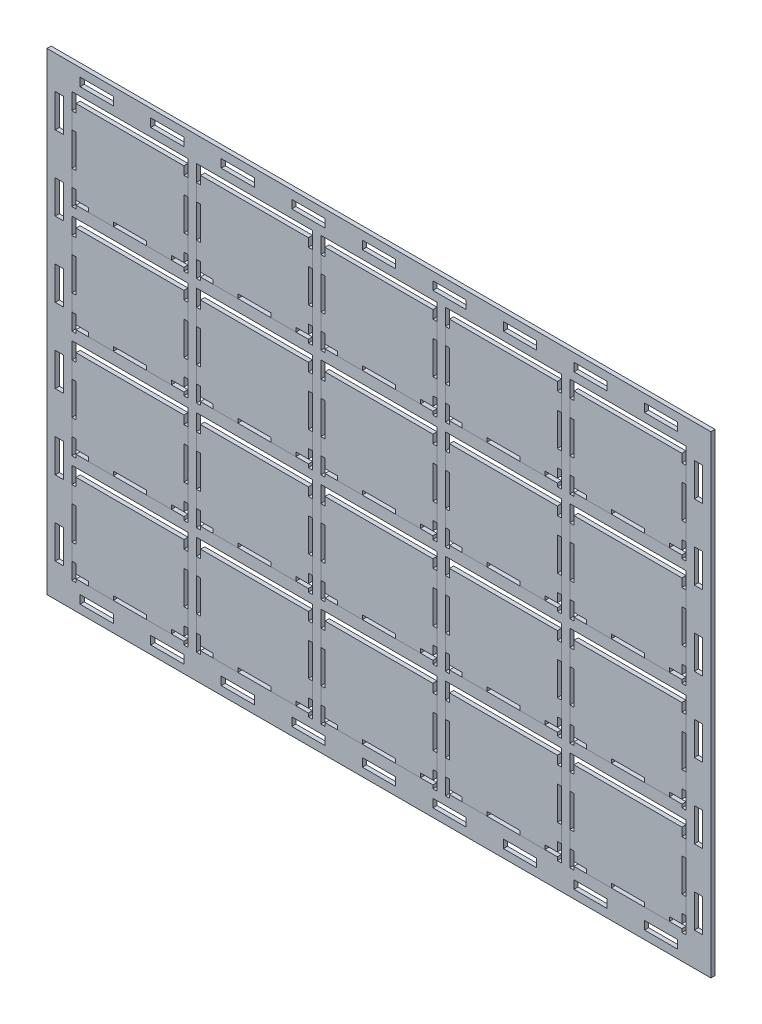
SolidWorks part; units mm, degrees
ref_plane "Front" through (0, 0, 0) normal (0, 0, 1) x (1, 0, 0)
ref_plane "Top" through (0, 0, 0) normal (0, 1, 0) x (1, 0, 0)
ref_plane "Right" through (0, 0, 0) normal (1, 0, 0) x (0, 0, -1)
sketch "Sketch1" plane through (0, 0, 0) normal (0, 0, 1) x (1, 0, 0)
  line L0 (-336.296, -110.6441) -> (-336.296, 164.3559) construction
  line L1 (-341.296, -115.6441) -> (58.704, -115.6441)
  line L2 (-341.296, -115.6441) -> (-341.296, 169.3559)
  line L3 (-341.296, 169.3559) -> (58.704, 169.3559)
  line L4 (58.704, -115.6441) -> (58.704, 169.3559)
  line L5 (-341.296, -115.6441) -> (58.704, 169.3559) construction
  line L6 (-341.296, 169.3559) -> (58.704, -115.6441) construction
  line L7 (-336.296, 164.3559) -> (53.704, 164.3559) construction
  line L8 (53.704, -110.6441) -> (53.704, 164.3559) construction
  line L9 (-336.296, -110.6441) -> (53.704, -110.6441) construction
  line L10 (-331.296, -105.6441) -> (-331.296, 159.3559) construction
  line L11 (-331.296, 159.3559) -> (48.704, 159.3559) construction
  line L12 (48.704, -105.6441) -> (48.704, 159.3559) construction
  line L13 (-331.296, -105.6441) -> (48.704, -105.6441) construction
  line L14 (-26.296, 96.3559) -> (43.704, 96.3559) construction
  line L15 (-26.296, 94.3559) -> (43.704, 94.3559) construction
  line L16 (-26.296, 94.3559) -> (-26.296, 154.3559) construction
  line L17 (-26.296, 154.3559) -> (43.704, 154.3559) construction
  line L18 (43.704, 94.3559) -> (43.704, 154.3559) construction
  line L19 (-26.296, 94.3559) -> (43.704, 154.3559) construction
  line L20 (-26.296, 154.3559) -> (43.704, 94.3559) construction
  line L21 (41.204, 154.3559) -> (41.204, 94.3559) construction
  line L22 (8.704, 134.2642) -> (8.704, 116.5512) construction
  line L23 (-23.796, 154.3559) -> (-23.796, 94.3559) construction
  line L24 (-26.296, 94.3559) -> (-26.296, 154.3559)
  line L25 (-26.296, 154.3559) -> (43.704, 154.3559)
  line L26 (43.704, 154.3559) -> (43.704, 94.3559)
  line L27 (43.704, 94.3559) -> (41.204, 94.3559)
  line L28 (41.204, 94.3559) -> (41.204, 96.3559)
  line L29 (-23.796, 94.3559) -> (-23.796, 96.3559)
  line L30 (-23.796, 96.3559) -> (41.204, 96.3559)
  line L31 (-23.796, 94.3559) -> (-26.296, 94.3559)
  line L32 (-23.796, 29.3559) -> (-26.296, 29.3559)
  line L33 (-26.296, 29.3559) -> (-26.296, 89.3559)
  line L34 (-26.296, 89.3559) -> (43.704, 89.3559)
  line L35 (43.704, 89.3559) -> (43.704, 29.3559)
  line L36 (43.704, 29.3559) -> (41.204, 29.3559)
  line L37 (41.204, 29.3559) -> (41.204, 31.3559)
  line L38 (-23.796, 31.3559) -> (41.204, 31.3559)
  line L39 (-23.796, 29.3559) -> (-23.796, 31.3559)
  line L40 (-23.796, -35.6441) -> (-26.296, -35.6441)
  line L41 (-26.296, -35.6441) -> (-26.296, 24.3559)
  line L42 (-26.296, 24.3559) -> (43.704, 24.3559)
  line L43 (43.704, 24.3559) -> (43.704, -35.6441)
  line L44 (43.704, -35.6441) -> (41.204, -35.6441)
  line L45 (41.204, -35.6441) -> (41.204, -33.6441)
  line L46 (-23.796, -33.6441) -> (41.204, -33.6441)
  line L47 (-23.796, -35.6441) -> (-23.796, -33.6441)
  line L48 (-23.796, -100.6441) -> (-26.296, -100.6441)
  line L49 (-26.296, -100.6441) -> (-26.296, -40.6441)
  line L50 (-26.296, -40.6441) -> (43.704, -40.6441)
  line L51 (43.704, -40.6441) -> (43.704, -100.6441)
  line L52 (43.704, -100.6441) -> (41.204, -100.6441)
  line L53 (41.204, -100.6441) -> (41.204, -98.6441)
  line L54 (-23.796, -98.6441) -> (41.204, -98.6441)
  line L55 (-23.796, -100.6441) -> (-23.796, -98.6441)
  line L56 (-98.796, 94.3559) -> (-101.296, 94.3559)
  line L57 (-101.296, 94.3559) -> (-101.296, 154.3559)
  line L58 (-101.296, 154.3559) -> (-31.296, 154.3559)
  line L59 (-31.296, 154.3559) -> (-31.296, 94.3559)
  line L60 (-31.296, 94.3559) -> (-33.796, 94.3559)
  line L61 (-33.796, 94.3559) -> (-33.796, 96.3559)
  line L62 (-98.796, 96.3559) -> (-33.796, 96.3559)
  line L63 (-98.796, 94.3559) -> (-98.796, 96.3559)
  line L64 (-98.796, 29.3559) -> (-101.296, 29.3559)
  line L65 (-101.296, 29.3559) -> (-101.296, 89.3559)
  line L66 (-101.296, 89.3559) -> (-31.296, 89.3559)
  line L67 (-31.296, 89.3559) -> (-31.296, 29.3559)
  line L68 (-31.296, 29.3559) -> (-33.796, 29.3559)
  line L69 (-33.796, 29.3559) -> (-33.796, 31.3559)
  line L70 (-98.796, 31.3559) -> (-33.796, 31.3559)
  line L71 (-98.796, 29.3559) -> (-98.796, 31.3559)
  line L72 (-98.796, -35.6441) -> (-101.296, -35.6441)
  line L73 (-101.296, -35.6441) -> (-101.296, 24.3559)
  line L74 (-101.296, 24.3559) -> (-31.296, 24.3559)
  line L75 (-31.296, 24.3559) -> (-31.296, -35.6441)
  line L76 (-31.296, -35.6441) -> (-33.796, -35.6441)
  line L77 (-33.796, -35.6441) -> (-33.796, -33.6441)
  line L78 (-98.796, -33.6441) -> (-33.796, -33.6441)
  line L79 (-98.796, -35.6441) -> (-98.796, -33.6441)
  line L80 (-98.796, -100.6441) -> (-101.296, -100.6441)
  line L81 (-101.296, -100.6441) -> (-101.296, -40.6441)
  line L82 (-101.296, -40.6441) -> (-31.296, -40.6441)
  line L83 (-31.296, -40.6441) -> (-31.296, -100.6441)
  line L84 (-31.296, -100.6441) -> (-33.796, -100.6441)
  line L85 (-33.796, -100.6441) -> (-33.796, -98.6441)
  line L86 (-98.796, -98.6441) -> (-33.796, -98.6441)
  line L87 (-98.796, -100.6441) -> (-98.796, -98.6441)
  line L88 (-173.796, 94.3559) -> (-176.296, 94.3559)
  line L89 (-176.296, 94.3559) -> (-176.296, 154.3559)
  line L90 (-176.296, 154.3559) -> (-106.296, 154.3559)
  line L91 (-106.296, 154.3559) -> (-106.296, 94.3559)
  line L92 (-106.296, 94.3559) -> (-108.796, 94.3559)
  line L93 (-108.796, 94.3559) -> (-108.796, 96.3559)
  line L94 (-173.796, 96.3559) -> (-108.796, 96.3559)
  line L95 (-173.796, 94.3559) -> (-173.796, 96.3559)
  line L96 (-173.796, 29.3559) -> (-176.296, 29.3559)
  line L97 (-176.296, 29.3559) -> (-176.296, 89.3559)
  line L98 (-176.296, 89.3559) -> (-106.296, 89.3559)
  line L99 (-106.296, 89.3559) -> (-106.296, 29.3559)
  line L100 (-106.296, 29.3559) -> (-108.796, 29.3559)
  line L101 (-108.796, 29.3559) -> (-108.796, 31.3559)
  line L102 (-173.796, 31.3559) -> (-108.796, 31.3559)
  line L103 (-173.796, 29.3559) -> (-173.796, 31.3559)
  line L104 (-173.796, -35.6441) -> (-176.296, -35.6441)
  line L105 (-176.296, -35.6441) -> (-176.296, 24.3559)
  line L106 (-176.296, 24.3559) -> (-106.296, 24.3559)
  line L107 (-106.296, 24.3559) -> (-106.296, -35.6441)
  line L108 (-106.296, -35.6441) -> (-108.796, -35.6441)
  line L109 (-108.796, -35.6441) -> (-108.796, -33.6441)
  line L110 (-173.796, -33.6441) -> (-108.796, -33.6441)
  line L111 (-173.796, -35.6441) -> (-173.796, -33.6441)
  line L112 (-173.796, -100.6441) -> (-176.296, -100.6441)
  line L113 (-176.296, -100.6441) -> (-176.296, -40.6441)
  line L114 (-176.296, -40.6441) -> (-106.296, -40.6441)
  line L115 (-106.296, -40.6441) -> (-106.296, -100.6441)
  line L116 (-106.296, -100.6441) -> (-108.796, -100.6441)
  line L117 (-108.796, -100.6441) -> (-108.796, -98.6441)
  line L118 (-173.796, -98.6441) -> (-108.796, -98.6441)
  line L119 (-173.796, -100.6441) -> (-173.796, -98.6441)
  line L120 (-248.796, 94.3559) -> (-251.296, 94.3559)
  line L121 (-251.296, 94.3559) -> (-251.296, 154.3559)
  line L122 (-251.296, 154.3559) -> (-181.296, 154.3559)
  line L123 (-181.296, 154.3559) -> (-181.296, 94.3559)
  line L124 (-181.296, 94.3559) -> (-183.796, 94.3559)
  line L125 (-183.796, 94.3559) -> (-183.796, 96.3559)
  line L126 (-248.796, 96.3559) -> (-183.796, 96.3559)
  line L127 (-248.796, 94.3559) -> (-248.796, 96.3559)
  line L128 (-248.796, 29.3559) -> (-251.296, 29.3559)
  line L129 (-251.296, 29.3559) -> (-251.296, 89.3559)
  line L130 (-251.296, 89.3559) -> (-181.296, 89.3559)
  line L131 (-181.296, 89.3559) -> (-181.296, 29.3559)
  line L132 (-181.296, 29.3559) -> (-183.796, 29.3559)
  line L133 (-183.796, 29.3559) -> (-183.796, 31.3559)
  line L134 (-248.796, 31.3559) -> (-183.796, 31.3559)
  line L135 (-248.796, 29.3559) -> (-248.796, 31.3559)
  line L136 (-248.796, -35.6441) -> (-251.296, -35.6441)
  line L137 (-251.296, -35.6441) -> (-251.296, 24.3559)
  line L138 (-251.296, 24.3559) -> (-181.296, 24.3559)
  line L139 (-181.296, 24.3559) -> (-181.296, -35.6441)
  line L140 (-181.296, -35.6441) -> (-183.796, -35.6441)
  line L141 (-183.796, -35.6441) -> (-183.796, -33.6441)
  line L142 (-248.796, -33.6441) -> (-183.796, -33.6441)
  line L143 (-248.796, -35.6441) -> (-248.796, -33.6441)
  line L144 (-248.796, -100.6441) -> (-251.296, -100.6441)
  line L145 (-251.296, -100.6441) -> (-251.296, -40.6441)
  line L146 (-251.296, -40.6441) -> (-181.296, -40.6441)
  line L147 (-181.296, -40.6441) -> (-181.296, -100.6441)
  line L148 (-181.296, -100.6441) -> (-183.796, -100.6441)
  line L149 (-183.796, -100.6441) -> (-183.796, -98.6441)
  line L150 (-248.796, -98.6441) -> (-183.796, -98.6441)
  line L151 (-248.796, -100.6441) -> (-248.796, -98.6441)
  line L152 (-323.796, 94.3559) -> (-326.296, 94.3559)
  line L153 (-326.296, 94.3559) -> (-326.296, 154.3559)
  line L154 (-326.296, 154.3559) -> (-256.296, 154.3559)
  line L155 (-256.296, 154.3559) -> (-256.296, 94.3559)
  line L156 (-256.296, 94.3559) -> (-258.796, 94.3559)
  line L157 (-258.796, 94.3559) -> (-258.796, 96.3559)
  line L158 (-323.796, 96.3559) -> (-258.796, 96.3559)
  line L159 (-323.796, 94.3559) -> (-323.796, 96.3559)
  line L160 (-323.796, 29.3559) -> (-326.296, 29.3559)
  line L161 (-326.296, 29.3559) -> (-326.296, 89.3559)
  line L162 (-326.296, 89.3559) -> (-256.296, 89.3559)
  line L163 (-256.296, 89.3559) -> (-256.296, 29.3559)
  line L164 (-256.296, 29.3559) -> (-258.796, 29.3559)
  line L165 (-258.796, 29.3559) -> (-258.796, 31.3559)
  line L166 (-323.796, 31.3559) -> (-258.796, 31.3559)
  line L167 (-323.796, 29.3559) -> (-323.796, 31.3559)
  line L168 (-323.796, -35.6441) -> (-326.296, -35.6441)
  line L169 (-326.296, -35.6441) -> (-326.296, 24.3559)
  line L170 (-326.296, 24.3559) -> (-256.296, 24.3559)
  line L171 (-256.296, 24.3559) -> (-256.296, -35.6441)
  line L172 (-256.296, -35.6441) -> (-258.796, -35.6441)
  line L173 (-258.796, -35.6441) -> (-258.796, -33.6441)
  line L174 (-323.796, -33.6441) -> (-258.796, -33.6441)
  line L175 (-323.796, -35.6441) -> (-323.796, -33.6441)
  line L176 (-323.796, -100.6441) -> (-326.296, -100.6441)
  line L177 (-326.296, -100.6441) -> (-326.296, -40.6441)
  line L178 (-326.296, -40.6441) -> (-256.296, -40.6441)
  line L179 (-256.296, -40.6441) -> (-256.296, -100.6441)
  line L180 (-256.296, -100.6441) -> (-258.796, -100.6441)
  line L181 (-258.796, -100.6441) -> (-258.796, -98.6441)
  line L182 (-323.796, -98.6441) -> (-258.796, -98.6441)
  line L183 (-323.796, -100.6441) -> (-323.796, -98.6441)
  line L184 (-119.2091, 26.8559) -> (-161.6715, 26.8559) construction
  line L185 (-321.296, 164.3559) -> (-301.296, 164.3559)
  line L186 (-321.296, 164.3559) -> (-321.296, 159.3559)
  line L187 (-321.296, 159.3559) -> (-301.296, 159.3559)
  line L188 (-301.296, 164.3559) -> (-301.296, 159.3559)
  line L189 (-321.296, 164.3559) -> (-301.296, 159.3559) construction
  line L190 (-321.296, 159.3559) -> (-301.296, 164.3559) construction
  line L191 (-141.296, 49.4928) -> (-141.296, 19.2296) construction
  line L192 (-321.296, -105.6441) -> (-301.296, -105.6441)
  line L193 (-301.296, -110.6441) -> (-301.296, -105.6441)
  line L194 (-321.296, -110.6441) -> (-301.296, -110.6441)
  line L195 (-321.296, -110.6441) -> (-321.296, -105.6441)
  line L196 (-278.796, 164.3559) -> (-278.796, 159.3559)
  line L197 (-278.796, 164.3559) -> (-258.796, 164.3559)
  line L198 (-258.796, 164.3559) -> (-258.796, 159.3559)
  line L199 (-278.796, 159.3559) -> (-258.796, 159.3559)
  line L200 (-278.796, -105.6441) -> (-258.796, -105.6441)
  line L201 (-258.796, -110.6441) -> (-258.796, -105.6441)
  line L202 (-278.796, -110.6441) -> (-258.796, -110.6441)
  line L203 (-278.796, -110.6441) -> (-278.796, -105.6441)
  line L204 (-236.296, 164.3559) -> (-236.296, 159.3559)
  line L205 (-236.296, 164.3559) -> (-216.296, 164.3559)
  line L206 (-216.296, 164.3559) -> (-216.296, 159.3559)
  line L207 (-236.296, 159.3559) -> (-216.296, 159.3559)
  line L208 (-236.296, -105.6441) -> (-216.296, -105.6441)
  line L209 (-216.296, -110.6441) -> (-216.296, -105.6441)
  line L210 (-236.296, -110.6441) -> (-216.296, -110.6441)
  line L211 (-236.296, -110.6441) -> (-236.296, -105.6441)
  line L212 (-193.796, 164.3559) -> (-193.796, 159.3559)
  line L213 (-193.796, 164.3559) -> (-173.796, 164.3559)
  line L214 (-173.796, 164.3559) -> (-173.796, 159.3559)
  line L215 (-193.796, 159.3559) -> (-173.796, 159.3559)
  line L216 (-193.796, -105.6441) -> (-173.796, -105.6441)
  line L217 (-173.796, -110.6441) -> (-173.796, -105.6441)
  line L218 (-193.796, -110.6441) -> (-173.796, -110.6441)
  line L219 (-193.796, -110.6441) -> (-193.796, -105.6441)
  line L220 (-151.296, 164.3559) -> (-151.296, 159.3559)
  line L221 (-151.296, 164.3559) -> (-131.296, 164.3559)
  line L222 (-131.296, 164.3559) -> (-131.296, 159.3559)
  line L223 (-151.296, 159.3559) -> (-131.296, 159.3559)
  line L224 (-151.296, -105.6441) -> (-131.296, -105.6441)
  line L225 (-131.296, -110.6441) -> (-131.296, -105.6441)
  line L226 (-151.296, -110.6441) -> (-131.296, -110.6441)
  line L227 (-151.296, -110.6441) -> (-151.296, -105.6441)
  line L228 (-108.796, 164.3559) -> (-108.796, 159.3559)
  line L229 (-108.796, 164.3559) -> (-88.796, 164.3559)
  line L230 (-88.796, 164.3559) -> (-88.796, 159.3559)
  line L231 (-108.796, 159.3559) -> (-88.796, 159.3559)
  line L232 (-108.796, -105.6441) -> (-88.796, -105.6441)
  line L233 (-88.796, -110.6441) -> (-88.796, -105.6441)
  line L234 (-108.796, -110.6441) -> (-88.796, -110.6441)
  line L235 (-108.796, -110.6441) -> (-108.796, -105.6441)
  line L236 (-66.296, 164.3559) -> (-66.296, 159.3559)
  line L237 (-66.296, 164.3559) -> (-46.296, 164.3559)
  line L238 (-46.296, 164.3559) -> (-46.296, 159.3559)
  line L239 (-66.296, 159.3559) -> (-46.296, 159.3559)
  line L240 (-66.296, -105.6441) -> (-46.296, -105.6441)
  line L241 (-46.296, -110.6441) -> (-46.296, -105.6441)
  line L242 (-66.296, -110.6441) -> (-46.296, -110.6441)
  line L243 (-66.296, -110.6441) -> (-66.296, -105.6441)
  line L244 (-23.796, 164.3559) -> (-23.796, 159.3559)
  line L245 (-23.796, 164.3559) -> (-3.796, 164.3559)
  line L246 (-3.796, 164.3559) -> (-3.796, 159.3559)
  line L247 (-23.796, 159.3559) -> (-3.796, 159.3559)
  line L248 (-23.796, -105.6441) -> (-3.796, -105.6441)
  line L249 (-3.796, -110.6441) -> (-3.796, -105.6441)
  line L250 (-23.796, -110.6441) -> (-3.796, -110.6441)
  line L251 (-23.796, -110.6441) -> (-23.796, -105.6441)
  line L252 (18.704, 164.3559) -> (18.704, 159.3559)
  line L253 (18.704, 164.3559) -> (38.704, 164.3559)
  line L254 (38.704, 164.3559) -> (38.704, 159.3559)
  line L255 (18.704, 159.3559) -> (38.704, 159.3559)
  line L256 (18.704, -105.6441) -> (38.704, -105.6441)
  line L257 (38.704, -110.6441) -> (38.704, -105.6441)
  line L258 (18.704, -110.6441) -> (38.704, -110.6441)
  line L259 (18.704, -110.6441) -> (18.704, -105.6441)
  line L260 (48.704, 129.3559) -> (53.704, 129.3559)
  line L261 (-331.296, 149.3559) -> (-336.296, 149.3559)
  line L262 (-331.296, 149.3559) -> (-331.296, 129.3559)
  line L263 (-331.296, 129.3559) -> (-336.296, 129.3559)
  line L264 (-336.296, 149.3559) -> (-336.296, 129.3559)
  line L265 (-331.296, 149.3559) -> (-336.296, 129.3559) construction
  line L266 (-331.296, 129.3559) -> (-336.296, 149.3559) construction
  line L267 (53.704, 149.3559) -> (53.704, 129.3559)
  line L268 (48.704, 149.3559) -> (53.704, 149.3559)
  line L269 (48.704, 149.3559) -> (48.704, 129.3559)
  line L270 (-331.296, 104.3559) -> (-331.296, 84.3559)
  line L271 (-331.296, 104.3559) -> (-336.296, 104.3559)
  line L272 (-336.296, 104.3559) -> (-336.296, 84.3559)
  line L273 (-331.296, 84.3559) -> (-336.296, 84.3559)
  line L274 (48.704, 84.3559) -> (53.704, 84.3559)
  line L275 (53.704, 104.3559) -> (53.704, 84.3559)
  line L276 (48.704, 104.3559) -> (53.704, 104.3559)
  line L277 (48.704, 104.3559) -> (48.704, 84.3559)
  line L278 (-331.296, 59.3559) -> (-331.296, 39.3559)
  line L279 (-331.296, 59.3559) -> (-336.296, 59.3559)
  line L280 (-336.296, 59.3559) -> (-336.296, 39.3559)
  line L281 (-331.296, 39.3559) -> (-336.296, 39.3559)
  line L282 (48.704, 39.3559) -> (53.704, 39.3559)
  line L283 (53.704, 59.3559) -> (53.704, 39.3559)
  line L284 (48.704, 59.3559) -> (53.704, 59.3559)
  line L285 (48.704, 59.3559) -> (48.704, 39.3559)
  line L286 (-331.296, 14.3559) -> (-331.296, -5.6441)
  line L287 (-331.296, 14.3559) -> (-336.296, 14.3559)
  line L288 (-336.296, 14.3559) -> (-336.296, -5.6441)
  line L289 (-331.296, -5.6441) -> (-336.296, -5.6441)
  line L290 (48.704, -5.6441) -> (53.704, -5.6441)
  line L291 (53.704, 14.3559) -> (53.704, -5.6441)
  line L292 (48.704, 14.3559) -> (53.704, 14.3559)
  line L293 (48.704, 14.3559) -> (48.704, -5.6441)
  line L294 (-331.296, -30.6441) -> (-331.296, -50.6441)
  line L295 (-331.296, -30.6441) -> (-336.296, -30.6441)
  line L296 (-336.296, -30.6441) -> (-336.296, -50.6441)
  line L297 (-331.296, -50.6441) -> (-336.296, -50.6441)
  line L298 (48.704, -50.6441) -> (53.704, -50.6441)
  line L299 (53.704, -30.6441) -> (53.704, -50.6441)
  line L300 (48.704, -30.6441) -> (53.704, -30.6441)
  line L301 (48.704, -30.6441) -> (48.704, -50.6441)
  line L302 (-331.296, -75.6441) -> (-331.296, -95.6441)
  line L303 (-331.296, -75.6441) -> (-336.296, -75.6441)
  line L304 (-336.296, -75.6441) -> (-336.296, -95.6441)
  line L305 (-331.296, -95.6441) -> (-336.296, -95.6441)
  line L306 (48.704, -95.6441) -> (53.704, -95.6441)
  line L307 (53.704, -75.6441) -> (53.704, -95.6441)
  line L308 (48.704, -75.6441) -> (53.704, -75.6441)
  line L309 (48.704, -75.6441) -> (48.704, -95.6441)
  line L310 (-26.296, 98.8559) -> (43.704, 98.8559) construction
  line L311 (-26.296, 94.3559) -> (43.704, 94.3559) construction
  line L312 (-26.296, 94.3559) -> (-26.296, 154.3559) construction
  line L313 (-26.296, 154.3559) -> (43.704, 154.3559) construction
  line L314 (43.704, 94.3559) -> (43.704, 154.3559) construction
  line L315 (-26.296, 94.3559) -> (43.704, 154.3559) construction
  line L316 (-26.296, 154.3559) -> (43.704, 94.3559) construction
  line L317 (8.704, 132.327) -> (8.704, 114.7588) construction
  line L318 (-16.296, 124.3559) -> (33.704, 124.3559) construction
  line L319 (-23.796, 154.3559) -> (-23.796, 94.3559) construction
  line L320 (41.204, 154.3559) -> (41.204, 94.3559) construction
  line L321 (33.704, 96.3559) -> (18.704, 96.3559)
  line L322 (-16.296, 98.8559) -> (-1.296, 98.8559) construction
  line L323 (-16.296, 98.8559) -> (-16.296, 96.3559)
  line L324 (-16.296, 96.3559) -> (-1.296, 96.3559)
  line L325 (-1.296, 98.8559) -> (-1.296, 96.3559)
  line L326 (-16.296, 98.8559) -> (-1.296, 96.3559) construction
  line L327 (-16.296, 96.3559) -> (-1.296, 98.8559) construction
  line L328 (18.704, 98.8559) -> (18.704, 96.3559)
  line L329 (33.704, 98.8559) -> (18.704, 98.8559) construction
  line L330 (33.704, 98.8559) -> (33.704, 96.3559)
  line L331 (-23.796, 114.3559) -> (-23.796, 134.3559)
  line L332 (-23.796, 134.3559) -> (-26.296, 134.3559)
  line L333 (-26.296, 134.3559) -> (-26.296, 144.3559)
  line L334 (-26.296, 144.3559) -> (-23.796, 144.3559)
  line L335 (-23.796, 144.3559) -> (-23.796, 154.3559) construction
  line L336 (-23.796, 154.3559) -> (41.204, 154.3559) construction
  line L337 (41.204, 144.3559) -> (41.204, 154.3559) construction
  line L338 (43.704, 144.3559) -> (41.204, 144.3559)
  line L339 (43.704, 134.3559) -> (43.704, 144.3559)
  line L340 (41.204, 134.3559) -> (43.704, 134.3559)
  line L341 (41.204, 114.3559) -> (41.204, 134.3559)
  line L342 (41.204, 114.3559) -> (43.704, 114.3559)
  line L343 (43.704, 114.3559) -> (43.704, 104.3559)
  line L344 (43.704, 104.3559) -> (41.204, 104.3559)
  line L345 (-23.796, 104.3559) -> (-23.796, 98.8559)
  line L346 (-23.796, 98.8559) -> (-16.296, 98.8559)
  line L347 (-26.296, 104.3559) -> (-23.796, 104.3559)
  line L348 (-26.296, 114.3559) -> (-26.296, 104.3559)
  line L349 (-23.796, 114.3559) -> (-26.296, 114.3559)
  line L350 (-23.796, 149.3559) -> (41.204, 149.3559)
  line L351 (-23.796, 149.3559) -> (-23.796, 144.3559)
  line L352 (41.204, 149.3559) -> (41.204, 144.3559)
  line L353 (-1.296, 98.8559) -> (18.704, 98.8559)
  line L354 (33.704, 98.8559) -> (41.204, 98.8559)
  line L355 (41.204, 98.8559) -> (41.204, 104.3559)
  line L356 (-1.296, 33.8559) -> (18.704, 33.8559)
  line L357 (18.704, 33.8559) -> (18.704, 31.3559)
  line L358 (33.704, 31.3559) -> (18.704, 31.3559)
  line L359 (33.704, 33.8559) -> (33.704, 31.3559)
  line L360 (33.704, 33.8559) -> (41.204, 33.8559)
  line L361 (41.204, 33.8559) -> (41.204, 39.3559)
  line L362 (43.704, 39.3559) -> (41.204, 39.3559)
  line L363 (43.704, 49.3559) -> (43.704, 39.3559)
  line L364 (41.204, 49.3559) -> (43.704, 49.3559)
  line L365 (41.204, 49.3559) -> (41.204, 69.3559)
  line L366 (41.204, 69.3559) -> (43.704, 69.3559)
  line L367 (43.704, 69.3559) -> (43.704, 79.3559)
  line L368 (43.704, 79.3559) -> (41.204, 79.3559)
  line L369 (41.204, 84.3559) -> (41.204, 79.3559)
  line L370 (-23.796, 84.3559) -> (41.204, 84.3559)
  line L371 (-23.796, 84.3559) -> (-23.796, 79.3559)
  line L372 (-26.296, 79.3559) -> (-23.796, 79.3559)
  line L373 (-26.296, 69.3559) -> (-26.296, 79.3559)
  line L374 (-23.796, 69.3559) -> (-26.296, 69.3559)
  line L375 (-23.796, 49.3559) -> (-23.796, 69.3559)
  line L376 (-23.796, 49.3559) -> (-26.296, 49.3559)
  line L377 (-26.296, 49.3559) -> (-26.296, 39.3559)
  line L378 (-26.296, 39.3559) -> (-23.796, 39.3559)
  line L379 (-23.796, 39.3559) -> (-23.796, 33.8559)
  line L380 (-23.796, 33.8559) -> (-16.296, 33.8559)
  line L381 (-16.296, 33.8559) -> (-16.296, 31.3559)
  line L382 (-16.296, 31.3559) -> (-1.296, 31.3559)
  line L383 (-1.296, 33.8559) -> (-1.296, 31.3559)
  line L384 (-1.296, -31.1441) -> (18.704, -31.1441)
  line L385 (18.704, -31.1441) -> (18.704, -33.6441)
  line L386 (33.704, -33.6441) -> (18.704, -33.6441)
  line L387 (33.704, -31.1441) -> (33.704, -33.6441)
  line L388 (33.704, -31.1441) -> (41.204, -31.1441)
  line L389 (41.204, -31.1441) -> (41.204, -25.6441)
  line L390 (43.704, -25.6441) -> (41.204, -25.6441)
  line L391 (43.704, -15.6441) -> (43.704, -25.6441)
  line L392 (41.204, -15.6441) -> (43.704, -15.6441)
  line L393 (41.204, -15.6441) -> (41.204, 4.3559)
  line L394 (41.204, 4.3559) -> (43.704, 4.3559)
  line L395 (43.704, 4.3559) -> (43.704, 14.3559)
  line L396 (43.704, 14.3559) -> (41.204, 14.3559)
  line L397 (41.204, 19.3559) -> (41.204, 14.3559)
  line L398 (-23.796, 19.3559) -> (41.204, 19.3559)
  line L399 (-23.796, 19.3559) -> (-23.796, 14.3559)
  line L400 (-26.296, 14.3559) -> (-23.796, 14.3559)
  line L401 (-26.296, 4.3559) -> (-26.296, 14.3559)
  line L402 (-23.796, 4.3559) -> (-26.296, 4.3559)
  line L403 (-23.796, -15.6441) -> (-23.796, 4.3559)
  line L404 (-23.796, -15.6441) -> (-26.296, -15.6441)
  line L405 (-26.296, -15.6441) -> (-26.296, -25.6441)
  line L406 (-26.296, -25.6441) -> (-23.796, -25.6441)
  line L407 (-23.796, -25.6441) -> (-23.796, -31.1441)
  line L408 (-23.796, -31.1441) -> (-16.296, -31.1441)
  line L409 (-16.296, -31.1441) -> (-16.296, -33.6441)
  line L410 (-16.296, -33.6441) -> (-1.296, -33.6441)
  line L411 (-1.296, -31.1441) -> (-1.296, -33.6441)
  line L412 (-1.296, -96.1441) -> (18.704, -96.1441)
  line L413 (18.704, -96.1441) -> (18.704, -98.6441)
  line L414 (33.704, -98.6441) -> (18.704, -98.6441)
  line L415 (33.704, -96.1441) -> (33.704, -98.6441)
  line L416 (33.704, -96.1441) -> (41.204, -96.1441)
  line L417 (41.204, -96.1441) -> (41.204, -90.6441)
  line L418 (43.704, -90.6441) -> (41.204, -90.6441)
  line L419 (43.704, -80.6441) -> (43.704, -90.6441)
  line L420 (41.204, -80.6441) -> (43.704, -80.6441)
  line L421 (41.204, -80.6441) -> (41.204, -60.6441)
  line L422 (41.204, -60.6441) -> (43.704, -60.6441)
  line L423 (43.704, -60.6441) -> (43.704, -50.6441)
  line L424 (43.704, -50.6441) -> (41.204, -50.6441)
  line L425 (41.204, -45.6441) -> (41.204, -50.6441)
  line L426 (-23.796, -45.6441) -> (41.204, -45.6441)
  line L427 (-23.796, -45.6441) -> (-23.796, -50.6441)
  line L428 (-26.296, -50.6441) -> (-23.796, -50.6441)
  line L429 (-26.296, -60.6441) -> (-26.296, -50.6441)
  line L430 (-23.796, -60.6441) -> (-26.296, -60.6441)
  line L431 (-23.796, -80.6441) -> (-23.796, -60.6441)
  line L432 (-23.796, -80.6441) -> (-26.296, -80.6441)
  line L433 (-26.296, -80.6441) -> (-26.296, -90.6441)
  line L434 (-26.296, -90.6441) -> (-23.796, -90.6441)
  line L435 (-23.796, -90.6441) -> (-23.796, -96.1441)
  line L436 (-23.796, -96.1441) -> (-16.296, -96.1441)
  line L437 (-16.296, -96.1441) -> (-16.296, -98.6441)
  line L438 (-16.296, -98.6441) -> (-1.296, -98.6441)
  line L439 (-1.296, -96.1441) -> (-1.296, -98.6441)
  line L440 (-76.296, 98.8559) -> (-56.296, 98.8559)
  line L441 (-56.296, 98.8559) -> (-56.296, 96.3559)
  line L442 (-41.296, 96.3559) -> (-56.296, 96.3559)
  line L443 (-41.296, 98.8559) -> (-41.296, 96.3559)
  line L444 (-41.296, 98.8559) -> (-33.796, 98.8559)
  line L445 (-33.796, 98.8559) -> (-33.796, 104.3559)
  line L446 (-31.296, 104.3559) -> (-33.796, 104.3559)
  line L447 (-31.296, 114.3559) -> (-31.296, 104.3559)
  line L448 (-33.796, 114.3559) -> (-31.296, 114.3559)
  line L449 (-33.796, 114.3559) -> (-33.796, 134.3559)
  line L450 (-33.796, 134.3559) -> (-31.296, 134.3559)
  line L451 (-31.296, 134.3559) -> (-31.296, 144.3559)
  line L452 (-31.296, 144.3559) -> (-33.796, 144.3559)
  line L453 (-33.796, 149.3559) -> (-33.796, 144.3559)
  line L454 (-98.796, 149.3559) -> (-33.796, 149.3559)
  line L455 (-98.796, 149.3559) -> (-98.796, 144.3559)
  line L456 (-101.296, 144.3559) -> (-98.796, 144.3559)
  line L457 (-101.296, 134.3559) -> (-101.296, 144.3559)
  line L458 (-98.796, 134.3559) -> (-101.296, 134.3559)
  line L459 (-98.796, 114.3559) -> (-98.796, 134.3559)
  line L460 (-98.796, 114.3559) -> (-101.296, 114.3559)
  line L461 (-101.296, 114.3559) -> (-101.296, 104.3559)
  line L462 (-101.296, 104.3559) -> (-98.796, 104.3559)
  line L463 (-98.796, 104.3559) -> (-98.796, 98.8559)
  line L464 (-98.796, 98.8559) -> (-91.296, 98.8559)
  line L465 (-91.296, 98.8559) -> (-91.296, 96.3559)
  line L466 (-91.296, 96.3559) -> (-76.296, 96.3559)
  line L467 (-76.296, 98.8559) -> (-76.296, 96.3559)
  line L468 (-76.296, 33.8559) -> (-56.296, 33.8559)
  line L469 (-56.296, 33.8559) -> (-56.296, 31.3559)
  line L470 (-41.296, 31.3559) -> (-56.296, 31.3559)
  line L471 (-41.296, 33.8559) -> (-41.296, 31.3559)
  line L472 (-41.296, 33.8559) -> (-33.796, 33.8559)
  line L473 (-33.796, 33.8559) -> (-33.796, 39.3559)
  line L474 (-31.296, 39.3559) -> (-33.796, 39.3559)
  line L475 (-31.296, 49.3559) -> (-31.296, 39.3559)
  line L476 (-33.796, 49.3559) -> (-31.296, 49.3559)
  line L477 (-33.796, 49.3559) -> (-33.796, 69.3559)
  line L478 (-33.796, 69.3559) -> (-31.296, 69.3559)
  line L479 (-31.296, 69.3559) -> (-31.296, 79.3559)
  line L480 (-31.296, 79.3559) -> (-33.796, 79.3559)
  line L481 (-33.796, 84.3559) -> (-33.796, 79.3559)
  line L482 (-98.796, 84.3559) -> (-33.796, 84.3559)
  line L483 (-98.796, 84.3559) -> (-98.796, 79.3559)
  line L484 (-101.296, 79.3559) -> (-98.796, 79.3559)
  line L485 (-101.296, 69.3559) -> (-101.296, 79.3559)
  line L486 (-98.796, 69.3559) -> (-101.296, 69.3559)
  line L487 (-98.796, 49.3559) -> (-98.796, 69.3559)
  line L488 (-98.796, 49.3559) -> (-101.296, 49.3559)
  line L489 (-101.296, 49.3559) -> (-101.296, 39.3559)
  line L490 (-101.296, 39.3559) -> (-98.796, 39.3559)
  line L491 (-98.796, 39.3559) -> (-98.796, 33.8559)
  line L492 (-98.796, 33.8559) -> (-91.296, 33.8559)
  line L493 (-91.296, 33.8559) -> (-91.296, 31.3559)
  line L494 (-91.296, 31.3559) -> (-76.296, 31.3559)
  line L495 (-76.296, 33.8559) -> (-76.296, 31.3559)
  line L496 (-76.296, -31.1441) -> (-56.296, -31.1441)
  line L497 (-56.296, -31.1441) -> (-56.296, -33.6441)
  line L498 (-41.296, -33.6441) -> (-56.296, -33.6441)
  line L499 (-41.296, -31.1441) -> (-41.296, -33.6441)
  line L500 (-41.296, -31.1441) -> (-33.796, -31.1441)
  line L501 (-33.796, -31.1441) -> (-33.796, -25.6441)
  line L502 (-31.296, -25.6441) -> (-33.796, -25.6441)
  line L503 (-31.296, -15.6441) -> (-31.296, -25.6441)
  line L504 (-33.796, -15.6441) -> (-31.296, -15.6441)
  line L505 (-33.796, -15.6441) -> (-33.796, 4.3559)
  line L506 (-33.796, 4.3559) -> (-31.296, 4.3559)
  line L507 (-31.296, 4.3559) -> (-31.296, 14.3559)
  line L508 (-31.296, 14.3559) -> (-33.796, 14.3559)
  line L509 (-33.796, 19.3559) -> (-33.796, 14.3559)
  line L510 (-98.796, 19.3559) -> (-33.796, 19.3559)
  line L511 (-98.796, 19.3559) -> (-98.796, 14.3559)
  line L512 (-101.296, 14.3559) -> (-98.796, 14.3559)
  line L513 (-101.296, 4.3559) -> (-101.296, 14.3559)
  line L514 (-98.796, 4.3559) -> (-101.296, 4.3559)
  line L515 (-98.796, -15.6441) -> (-98.796, 4.3559)
  line L516 (-98.796, -15.6441) -> (-101.296, -15.6441)
  line L517 (-101.296, -15.6441) -> (-101.296, -25.6441)
  line L518 (-101.296, -25.6441) -> (-98.796, -25.6441)
  line L519 (-98.796, -25.6441) -> (-98.796, -31.1441)
  line L520 (-98.796, -31.1441) -> (-91.296, -31.1441)
  line L521 (-91.296, -31.1441) -> (-91.296, -33.6441)
  line L522 (-91.296, -33.6441) -> (-76.296, -33.6441)
  line L523 (-76.296, -31.1441) -> (-76.296, -33.6441)
  line L524 (-76.296, -96.1441) -> (-56.296, -96.1441)
  line L525 (-56.296, -96.1441) -> (-56.296, -98.6441)
  line L526 (-41.296, -98.6441) -> (-56.296, -98.6441)
  line L527 (-41.296, -96.1441) -> (-41.296, -98.6441)
  line L528 (-41.296, -96.1441) -> (-33.796, -96.1441)
  line L529 (-33.796, -96.1441) -> (-33.796, -90.6441)
  line L530 (-31.296, -90.6441) -> (-33.796, -90.6441)
  line L531 (-31.296, -80.6441) -> (-31.296, -90.6441)
  line L532 (-33.796, -80.6441) -> (-31.296, -80.6441)
  line L533 (-33.796, -80.6441) -> (-33.796, -60.6441)
  line L534 (-33.796, -60.6441) -> (-31.296, -60.6441)
  line L535 (-31.296, -60.6441) -> (-31.296, -50.6441)
  line L536 (-31.296, -50.6441) -> (-33.796, -50.6441)
  line L537 (-33.796, -45.6441) -> (-33.796, -50.6441)
  line L538 (-98.796, -45.6441) -> (-33.796, -45.6441)
  line L539 (-98.796, -45.6441) -> (-98.796, -50.6441)
  line L540 (-101.296, -50.6441) -> (-98.796, -50.6441)
  line L541 (-101.296, -60.6441) -> (-101.296, -50.6441)
  line L542 (-98.796, -60.6441) -> (-101.296, -60.6441)
  line L543 (-98.796, -80.6441) -> (-98.796, -60.6441)
  line L544 (-98.796, -80.6441) -> (-101.296, -80.6441)
  line L545 (-101.296, -80.6441) -> (-101.296, -90.6441)
  line L546 (-101.296, -90.6441) -> (-98.796, -90.6441)
  line L547 (-98.796, -90.6441) -> (-98.796, -96.1441)
  line L548 (-98.796, -96.1441) -> (-91.296, -96.1441)
  line L549 (-91.296, -96.1441) -> (-91.296, -98.6441)
  line L550 (-91.296, -98.6441) -> (-76.296, -98.6441)
  line L551 (-76.296, -96.1441) -> (-76.296, -98.6441)
  line L552 (-151.296, 98.8559) -> (-131.296, 98.8559)
  line L553 (-131.296, 98.8559) -> (-131.296, 96.3559)
  line L554 (-116.296, 96.3559) -> (-131.296, 96.3559)
  line L555 (-116.296, 98.8559) -> (-116.296, 96.3559)
  line L556 (-116.296, 98.8559) -> (-108.796, 98.8559)
  line L557 (-108.796, 98.8559) -> (-108.796, 104.3559)
  line L558 (-106.296, 104.3559) -> (-108.796, 104.3559)
  line L559 (-106.296, 114.3559) -> (-106.296, 104.3559)
  line L560 (-108.796, 114.3559) -> (-106.296, 114.3559)
  line L561 (-108.796, 114.3559) -> (-108.796, 134.3559)
  line L562 (-108.796, 134.3559) -> (-106.296, 134.3559)
  line L563 (-106.296, 134.3559) -> (-106.296, 144.3559)
  line L564 (-106.296, 144.3559) -> (-108.796, 144.3559)
  line L565 (-108.796, 149.3559) -> (-108.796, 144.3559)
  line L566 (-173.796, 149.3559) -> (-108.796, 149.3559)
  line L567 (-173.796, 149.3559) -> (-173.796, 144.3559)
  line L568 (-176.296, 144.3559) -> (-173.796, 144.3559)
  line L569 (-176.296, 134.3559) -> (-176.296, 144.3559)
  line L570 (-173.796, 134.3559) -> (-176.296, 134.3559)
  line L571 (-173.796, 114.3559) -> (-173.796, 134.3559)
  line L572 (-173.796, 114.3559) -> (-176.296, 114.3559)
  line L573 (-176.296, 114.3559) -> (-176.296, 104.3559)
  line L574 (-176.296, 104.3559) -> (-173.796, 104.3559)
  line L575 (-173.796, 104.3559) -> (-173.796, 98.8559)
  line L576 (-173.796, 98.8559) -> (-166.296, 98.8559)
  line L577 (-166.296, 98.8559) -> (-166.296, 96.3559)
  line L578 (-166.296, 96.3559) -> (-151.296, 96.3559)
  line L579 (-151.296, 98.8559) -> (-151.296, 96.3559)
  line L580 (-151.296, 33.8559) -> (-131.296, 33.8559)
  line L581 (-131.296, 33.8559) -> (-131.296, 31.3559)
  line L582 (-116.296, 31.3559) -> (-131.296, 31.3559)
  line L583 (-116.296, 33.8559) -> (-116.296, 31.3559)
  line L584 (-116.296, 33.8559) -> (-108.796, 33.8559)
  line L585 (-108.796, 33.8559) -> (-108.796, 39.3559)
  line L586 (-106.296, 39.3559) -> (-108.796, 39.3559)
  line L587 (-106.296, 49.3559) -> (-106.296, 39.3559)
  line L588 (-108.796, 49.3559) -> (-106.296, 49.3559)
  line L589 (-108.796, 49.3559) -> (-108.796, 69.3559)
  line L590 (-108.796, 69.3559) -> (-106.296, 69.3559)
  line L591 (-106.296, 69.3559) -> (-106.296, 79.3559)
  line L592 (-106.296, 79.3559) -> (-108.796, 79.3559)
  line L593 (-108.796, 84.3559) -> (-108.796, 79.3559)
  line L594 (-173.796, 84.3559) -> (-108.796, 84.3559)
  line L595 (-173.796, 84.3559) -> (-173.796, 79.3559)
  line L596 (-176.296, 79.3559) -> (-173.796, 79.3559)
  line L597 (-176.296, 69.3559) -> (-176.296, 79.3559)
  line L598 (-173.796, 69.3559) -> (-176.296, 69.3559)
  line L599 (-173.796, 49.3559) -> (-173.796, 69.3559)
  line L600 (-173.796, 49.3559) -> (-176.296, 49.3559)
  line L601 (-176.296, 49.3559) -> (-176.296, 39.3559)
  line L602 (-176.296, 39.3559) -> (-173.796, 39.3559)
  line L603 (-173.796, 39.3559) -> (-173.796, 33.8559)
  line L604 (-173.796, 33.8559) -> (-166.296, 33.8559)
  line L605 (-166.296, 33.8559) -> (-166.296, 31.3559)
  line L606 (-166.296, 31.3559) -> (-151.296, 31.3559)
  line L607 (-151.296, 33.8559) -> (-151.296, 31.3559)
  line L608 (-151.296, -31.1441) -> (-131.296, -31.1441)
  line L609 (-131.296, -31.1441) -> (-131.296, -33.6441)
  line L610 (-116.296, -33.6441) -> (-131.296, -33.6441)
  line L611 (-116.296, -31.1441) -> (-116.296, -33.6441)
  line L612 (-116.296, -31.1441) -> (-108.796, -31.1441)
  line L613 (-108.796, -31.1441) -> (-108.796, -25.6441)
  line L614 (-106.296, -25.6441) -> (-108.796, -25.6441)
  line L615 (-106.296, -15.6441) -> (-106.296, -25.6441)
  line L616 (-108.796, -15.6441) -> (-106.296, -15.6441)
  line L617 (-108.796, -15.6441) -> (-108.796, 4.3559)
  line L618 (-108.796, 4.3559) -> (-106.296, 4.3559)
  line L619 (-106.296, 4.3559) -> (-106.296, 14.3559)
  line L620 (-106.296, 14.3559) -> (-108.796, 14.3559)
  line L621 (-108.796, 19.3559) -> (-108.796, 14.3559)
  line L622 (-173.796, 19.3559) -> (-108.796, 19.3559)
  line L623 (-173.796, 19.3559) -> (-173.796, 14.3559)
  line L624 (-176.296, 14.3559) -> (-173.796, 14.3559)
  line L625 (-176.296, 4.3559) -> (-176.296, 14.3559)
  line L626 (-173.796, 4.3559) -> (-176.296, 4.3559)
  line L627 (-173.796, -15.6441) -> (-173.796, 4.3559)
  line L628 (-173.796, -15.6441) -> (-176.296, -15.6441)
  line L629 (-176.296, -15.6441) -> (-176.296, -25.6441)
  line L630 (-176.296, -25.6441) -> (-173.796, -25.6441)
  line L631 (-173.796, -25.6441) -> (-173.796, -31.1441)
  line L632 (-173.796, -31.1441) -> (-166.296, -31.1441)
  line L633 (-166.296, -31.1441) -> (-166.296, -33.6441)
  line L634 (-166.296, -33.6441) -> (-151.296, -33.6441)
  line L635 (-151.296, -31.1441) -> (-151.296, -33.6441)
  line L636 (-151.296, -96.1441) -> (-131.296, -96.1441)
  line L637 (-131.296, -96.1441) -> (-131.296, -98.6441)
  line L638 (-116.296, -98.6441) -> (-131.296, -98.6441)
  line L639 (-116.296, -96.1441) -> (-116.296, -98.6441)
  line L640 (-116.296, -96.1441) -> (-108.796, -96.1441)
  line L641 (-108.796, -96.1441) -> (-108.796, -90.6441)
  line L642 (-106.296, -90.6441) -> (-108.796, -90.6441)
  line L643 (-106.296, -80.6441) -> (-106.296, -90.6441)
  line L644 (-108.796, -80.6441) -> (-106.296, -80.6441)
  line L645 (-108.796, -80.6441) -> (-108.796, -60.6441)
  line L646 (-108.796, -60.6441) -> (-106.296, -60.6441)
  line L647 (-106.296, -60.6441) -> (-106.296, -50.6441)
  line L648 (-106.296, -50.6441) -> (-108.796, -50.6441)
  line L649 (-108.796, -45.6441) -> (-108.796, -50.6441)
  line L650 (-173.796, -45.6441) -> (-108.796, -45.6441)
  line L651 (-173.796, -45.6441) -> (-173.796, -50.6441)
  line L652 (-176.296, -50.6441) -> (-173.796, -50.6441)
  line L653 (-176.296, -60.6441) -> (-176.296, -50.6441)
  line L654 (-173.796, -60.6441) -> (-176.296, -60.6441)
  line L655 (-173.796, -80.6441) -> (-173.796, -60.6441)
  line L656 (-173.796, -80.6441) -> (-176.296, -80.6441)
  line L657 (-176.296, -80.6441) -> (-176.296, -90.6441)
  line L658 (-176.296, -90.6441) -> (-173.796, -90.6441)
  line L659 (-173.796, -90.6441) -> (-173.796, -96.1441)
  line L660 (-173.796, -96.1441) -> (-166.296, -96.1441)
  line L661 (-166.296, -96.1441) -> (-166.296, -98.6441)
  line L662 (-166.296, -98.6441) -> (-151.296, -98.6441)
  line L663 (-151.296, -96.1441) -> (-151.296, -98.6441)
  line L664 (-226.296, 98.8559) -> (-206.296, 98.8559)
  line L665 (-206.296, 98.8559) -> (-206.296, 96.3559)
  line L666 (-191.296, 96.3559) -> (-206.296, 96.3559)
  line L667 (-191.296, 98.8559) -> (-191.296, 96.3559)
  line L668 (-191.296, 98.8559) -> (-183.796, 98.8559)
  line L669 (-183.796, 98.8559) -> (-183.796, 104.3559)
  line L670 (-181.296, 104.3559) -> (-183.796, 104.3559)
  line L671 (-181.296, 114.3559) -> (-181.296, 104.3559)
  line L672 (-183.796, 114.3559) -> (-181.296, 114.3559)
  line L673 (-183.796, 114.3559) -> (-183.796, 134.3559)
  line L674 (-183.796, 134.3559) -> (-181.296, 134.3559)
  line L675 (-181.296, 134.3559) -> (-181.296, 144.3559)
  line L676 (-181.296, 144.3559) -> (-183.796, 144.3559)
  line L677 (-183.796, 149.3559) -> (-183.796, 144.3559)
  line L678 (-248.796, 149.3559) -> (-183.796, 149.3559)
  line L679 (-248.796, 149.3559) -> (-248.796, 144.3559)
  line L680 (-251.296, 144.3559) -> (-248.796, 144.3559)
  line L681 (-251.296, 134.3559) -> (-251.296, 144.3559)
  line L682 (-248.796, 134.3559) -> (-251.296, 134.3559)
  line L683 (-248.796, 114.3559) -> (-248.796, 134.3559)
  line L684 (-248.796, 114.3559) -> (-251.296, 114.3559)
  line L685 (-251.296, 114.3559) -> (-251.296, 104.3559)
  line L686 (-251.296, 104.3559) -> (-248.796, 104.3559)
  line L687 (-248.796, 104.3559) -> (-248.796, 98.8559)
  line L688 (-248.796, 98.8559) -> (-241.296, 98.8559)
  line L689 (-241.296, 98.8559) -> (-241.296, 96.3559)
  line L690 (-241.296, 96.3559) -> (-226.296, 96.3559)
  line L691 (-226.296, 98.8559) -> (-226.296, 96.3559)
  line L692 (-226.296, 33.8559) -> (-206.296, 33.8559)
  line L693 (-206.296, 33.8559) -> (-206.296, 31.3559)
  line L694 (-191.296, 31.3559) -> (-206.296, 31.3559)
  line L695 (-191.296, 33.8559) -> (-191.296, 31.3559)
  line L696 (-191.296, 33.8559) -> (-183.796, 33.8559)
  line L697 (-183.796, 33.8559) -> (-183.796, 39.3559)
  line L698 (-181.296, 39.3559) -> (-183.796, 39.3559)
  line L699 (-181.296, 49.3559) -> (-181.296, 39.3559)
  line L700 (-183.796, 49.3559) -> (-181.296, 49.3559)
  line L701 (-183.796, 49.3559) -> (-183.796, 69.3559)
  line L702 (-183.796, 69.3559) -> (-181.296, 69.3559)
  line L703 (-181.296, 69.3559) -> (-181.296, 79.3559)
  line L704 (-181.296, 79.3559) -> (-183.796, 79.3559)
  line L705 (-183.796, 84.3559) -> (-183.796, 79.3559)
  line L706 (-248.796, 84.3559) -> (-183.796, 84.3559)
  line L707 (-248.796, 84.3559) -> (-248.796, 79.3559)
  line L708 (-251.296, 79.3559) -> (-248.796, 79.3559)
  line L709 (-251.296, 69.3559) -> (-251.296, 79.3559)
  line L710 (-248.796, 69.3559) -> (-251.296, 69.3559)
  line L711 (-248.796, 49.3559) -> (-248.796, 69.3559)
  line L712 (-248.796, 49.3559) -> (-251.296, 49.3559)
  line L713 (-251.296, 49.3559) -> (-251.296, 39.3559)
  line L714 (-251.296, 39.3559) -> (-248.796, 39.3559)
  line L715 (-248.796, 39.3559) -> (-248.796, 33.8559)
  line L716 (-248.796, 33.8559) -> (-241.296, 33.8559)
  line L717 (-241.296, 33.8559) -> (-241.296, 31.3559)
  line L718 (-241.296, 31.3559) -> (-226.296, 31.3559)
  line L719 (-226.296, 33.8559) -> (-226.296, 31.3559)
  line L720 (-226.296, -31.1441) -> (-206.296, -31.1441)
  line L721 (-206.296, -31.1441) -> (-206.296, -33.6441)
  line L722 (-191.296, -33.6441) -> (-206.296, -33.6441)
  line L723 (-191.296, -31.1441) -> (-191.296, -33.6441)
  line L724 (-191.296, -31.1441) -> (-183.796, -31.1441)
  line L725 (-183.796, -31.1441) -> (-183.796, -25.6441)
  line L726 (-181.296, -25.6441) -> (-183.796, -25.6441)
  line L727 (-181.296, -15.6441) -> (-181.296, -25.6441)
  line L728 (-183.796, -15.6441) -> (-181.296, -15.6441)
  line L729 (-183.796, -15.6441) -> (-183.796, 4.3559)
  line L730 (-183.796, 4.3559) -> (-181.296, 4.3559)
  line L731 (-181.296, 4.3559) -> (-181.296, 14.3559)
  line L732 (-181.296, 14.3559) -> (-183.796, 14.3559)
  line L733 (-183.796, 19.3559) -> (-183.796, 14.3559)
  line L734 (-248.796, 19.3559) -> (-183.796, 19.3559)
  line L735 (-248.796, 19.3559) -> (-248.796, 14.3559)
  line L736 (-251.296, 14.3559) -> (-248.796, 14.3559)
  line L737 (-251.296, 4.3559) -> (-251.296, 14.3559)
  line L738 (-248.796, 4.3559) -> (-251.296, 4.3559)
  line L739 (-248.796, -15.6441) -> (-248.796, 4.3559)
  line L740 (-248.796, -15.6441) -> (-251.296, -15.6441)
  line L741 (-251.296, -15.6441) -> (-251.296, -25.6441)
  line L742 (-251.296, -25.6441) -> (-248.796, -25.6441)
  line L743 (-248.796, -25.6441) -> (-248.796, -31.1441)
  line L744 (-248.796, -31.1441) -> (-241.296, -31.1441)
  line L745 (-241.296, -31.1441) -> (-241.296, -33.6441)
  line L746 (-241.296, -33.6441) -> (-226.296, -33.6441)
  line L747 (-226.296, -31.1441) -> (-226.296, -33.6441)
  line L748 (-226.296, -96.1441) -> (-206.296, -96.1441)
  line L749 (-206.296, -96.1441) -> (-206.296, -98.6441)
  line L750 (-191.296, -98.6441) -> (-206.296, -98.6441)
  line L751 (-191.296, -96.1441) -> (-191.296, -98.6441)
  line L752 (-191.296, -96.1441) -> (-183.796, -96.1441)
  line L753 (-183.796, -96.1441) -> (-183.796, -90.6441)
  line L754 (-181.296, -90.6441) -> (-183.796, -90.6441)
  line L755 (-181.296, -80.6441) -> (-181.296, -90.6441)
  line L756 (-183.796, -80.6441) -> (-181.296, -80.6441)
  line L757 (-183.796, -80.6441) -> (-183.796, -60.6441)
  line L758 (-183.796, -60.6441) -> (-181.296, -60.6441)
  line L759 (-181.296, -60.6441) -> (-181.296, -50.6441)
  line L760 (-181.296, -50.6441) -> (-183.796, -50.6441)
  line L761 (-183.796, -45.6441) -> (-183.796, -50.6441)
  line L762 (-248.796, -45.6441) -> (-183.796, -45.6441)
  line L763 (-248.796, -45.6441) -> (-248.796, -50.6441)
  line L764 (-251.296, -50.6441) -> (-248.796, -50.6441)
  line L765 (-251.296, -60.6441) -> (-251.296, -50.6441)
  line L766 (-248.796, -60.6441) -> (-251.296, -60.6441)
  line L767 (-248.796, -80.6441) -> (-248.796, -60.6441)
  line L768 (-248.796, -80.6441) -> (-251.296, -80.6441)
  line L769 (-251.296, -80.6441) -> (-251.296, -90.6441)
  line L770 (-251.296, -90.6441) -> (-248.796, -90.6441)
  line L771 (-248.796, -90.6441) -> (-248.796, -96.1441)
  line L772 (-248.796, -96.1441) -> (-241.296, -96.1441)
  line L773 (-241.296, -96.1441) -> (-241.296, -98.6441)
  line L774 (-241.296, -98.6441) -> (-226.296, -98.6441)
  line L775 (-226.296, -96.1441) -> (-226.296, -98.6441)
  line L776 (-301.296, 98.8559) -> (-281.296, 98.8559)
  line L777 (-281.296, 98.8559) -> (-281.296, 96.3559)
  line L778 (-266.296, 96.3559) -> (-281.296, 96.3559)
  line L779 (-266.296, 98.8559) -> (-266.296, 96.3559)
  line L780 (-266.296, 98.8559) -> (-258.796, 98.8559)
  line L781 (-258.796, 98.8559) -> (-258.796, 104.3559)
  line L782 (-256.296, 104.3559) -> (-258.796, 104.3559)
  line L783 (-256.296, 114.3559) -> (-256.296, 104.3559)
  line L784 (-258.796, 114.3559) -> (-256.296, 114.3559)
  line L785 (-258.796, 114.3559) -> (-258.796, 134.3559)
  line L786 (-258.796, 134.3559) -> (-256.296, 134.3559)
  line L787 (-256.296, 134.3559) -> (-256.296, 144.3559)
  line L788 (-256.296, 144.3559) -> (-258.796, 144.3559)
  line L789 (-258.796, 149.3559) -> (-258.796, 144.3559)
  line L790 (-323.796, 149.3559) -> (-258.796, 149.3559)
  line L791 (-323.796, 149.3559) -> (-323.796, 144.3559)
  line L792 (-326.296, 144.3559) -> (-323.796, 144.3559)
  line L793 (-326.296, 134.3559) -> (-326.296, 144.3559)
  line L794 (-323.796, 134.3559) -> (-326.296, 134.3559)
  line L795 (-323.796, 114.3559) -> (-323.796, 134.3559)
  line L796 (-323.796, 114.3559) -> (-326.296, 114.3559)
  line L797 (-326.296, 114.3559) -> (-326.296, 104.3559)
  line L798 (-326.296, 104.3559) -> (-323.796, 104.3559)
  line L799 (-323.796, 104.3559) -> (-323.796, 98.8559)
  line L800 (-323.796, 98.8559) -> (-316.296, 98.8559)
  line L801 (-316.296, 98.8559) -> (-316.296, 96.3559)
  line L802 (-316.296, 96.3559) -> (-301.296, 96.3559)
  line L803 (-301.296, 98.8559) -> (-301.296, 96.3559)
  line L804 (-301.296, 33.8559) -> (-281.296, 33.8559)
  line L805 (-281.296, 33.8559) -> (-281.296, 31.3559)
  line L806 (-266.296, 31.3559) -> (-281.296, 31.3559)
  line L807 (-266.296, 33.8559) -> (-266.296, 31.3559)
  line L808 (-266.296, 33.8559) -> (-258.796, 33.8559)
  line L809 (-258.796, 33.8559) -> (-258.796, 39.3559)
  line L810 (-256.296, 39.3559) -> (-258.796, 39.3559)
  line L811 (-256.296, 49.3559) -> (-256.296, 39.3559)
  line L812 (-258.796, 49.3559) -> (-256.296, 49.3559)
  line L813 (-258.796, 49.3559) -> (-258.796, 69.3559)
  line L814 (-258.796, 69.3559) -> (-256.296, 69.3559)
  line L815 (-256.296, 69.3559) -> (-256.296, 79.3559)
  line L816 (-256.296, 79.3559) -> (-258.796, 79.3559)
  line L817 (-258.796, 84.3559) -> (-258.796, 79.3559)
  line L818 (-323.796, 84.3559) -> (-258.796, 84.3559)
  line L819 (-323.796, 84.3559) -> (-323.796, 79.3559)
  line L820 (-326.296, 79.3559) -> (-323.796, 79.3559)
  line L821 (-326.296, 69.3559) -> (-326.296, 79.3559)
  line L822 (-323.796, 69.3559) -> (-326.296, 69.3559)
  line L823 (-323.796, 49.3559) -> (-323.796, 69.3559)
  line L824 (-323.796, 49.3559) -> (-326.296, 49.3559)
  line L825 (-326.296, 49.3559) -> (-326.296, 39.3559)
  line L826 (-326.296, 39.3559) -> (-323.796, 39.3559)
  line L827 (-323.796, 39.3559) -> (-323.796, 33.8559)
  line L828 (-323.796, 33.8559) -> (-316.296, 33.8559)
  line L829 (-316.296, 33.8559) -> (-316.296, 31.3559)
  line L830 (-316.296, 31.3559) -> (-301.296, 31.3559)
  line L831 (-301.296, 33.8559) -> (-301.296, 31.3559)
  line L832 (-301.296, -31.1441) -> (-281.296, -31.1441)
  line L833 (-281.296, -31.1441) -> (-281.296, -33.6441)
  line L834 (-266.296, -33.6441) -> (-281.296, -33.6441)
  line L835 (-266.296, -31.1441) -> (-266.296, -33.6441)
  line L836 (-266.296, -31.1441) -> (-258.796, -31.1441)
  line L837 (-258.796, -31.1441) -> (-258.796, -25.6441)
  line L838 (-256.296, -25.6441) -> (-258.796, -25.6441)
  line L839 (-256.296, -15.6441) -> (-256.296, -25.6441)
  line L840 (-258.796, -15.6441) -> (-256.296, -15.6441)
  line L841 (-258.796, -15.6441) -> (-258.796, 4.3559)
  line L842 (-258.796, 4.3559) -> (-256.296, 4.3559)
  line L843 (-256.296, 4.3559) -> (-256.296, 14.3559)
  line L844 (-256.296, 14.3559) -> (-258.796, 14.3559)
  line L845 (-258.796, 19.3559) -> (-258.796, 14.3559)
  line L846 (-323.796, 19.3559) -> (-258.796, 19.3559)
  line L847 (-323.796, 19.3559) -> (-323.796, 14.3559)
  line L848 (-326.296, 14.3559) -> (-323.796, 14.3559)
  line L849 (-326.296, 4.3559) -> (-326.296, 14.3559)
  line L850 (-323.796, 4.3559) -> (-326.296, 4.3559)
  line L851 (-323.796, -15.6441) -> (-323.796, 4.3559)
  line L852 (-323.796, -15.6441) -> (-326.296, -15.6441)
  line L853 (-326.296, -15.6441) -> (-326.296, -25.6441)
  line L854 (-326.296, -25.6441) -> (-323.796, -25.6441)
  line L855 (-323.796, -25.6441) -> (-323.796, -31.1441)
  line L856 (-323.796, -31.1441) -> (-316.296, -31.1441)
  line L857 (-316.296, -31.1441) -> (-316.296, -33.6441)
  line L858 (-316.296, -33.6441) -> (-301.296, -33.6441)
  line L859 (-301.296, -31.1441) -> (-301.296, -33.6441)
  line L860 (-301.296, -96.1441) -> (-281.296, -96.1441)
  line L861 (-281.296, -96.1441) -> (-281.296, -98.6441)
  line L862 (-266.296, -98.6441) -> (-281.296, -98.6441)
  line L863 (-266.296, -96.1441) -> (-266.296, -98.6441)
  line L864 (-266.296, -96.1441) -> (-258.796, -96.1441)
  line L865 (-258.796, -96.1441) -> (-258.796, -90.6441)
  line L866 (-256.296, -90.6441) -> (-258.796, -90.6441)
  line L867 (-256.296, -80.6441) -> (-256.296, -90.6441)
  line L868 (-258.796, -80.6441) -> (-256.296, -80.6441)
  line L869 (-258.796, -80.6441) -> (-258.796, -60.6441)
  line L870 (-258.796, -60.6441) -> (-256.296, -60.6441)
  line L871 (-256.296, -60.6441) -> (-256.296, -50.6441)
  line L872 (-256.296, -50.6441) -> (-258.796, -50.6441)
  line L873 (-258.796, -45.6441) -> (-258.796, -50.6441)
  line L874 (-323.796, -45.6441) -> (-258.796, -45.6441)
  line L875 (-323.796, -45.6441) -> (-323.796, -50.6441)
  line L876 (-326.296, -50.6441) -> (-323.796, -50.6441)
  line L877 (-326.296, -60.6441) -> (-326.296, -50.6441)
  line L878 (-323.796, -60.6441) -> (-326.296, -60.6441)
  line L879 (-323.796, -80.6441) -> (-323.796, -60.6441)
  line L880 (-323.796, -80.6441) -> (-326.296, -80.6441)
  line L881 (-326.296, -80.6441) -> (-326.296, -90.6441)
  line L882 (-326.296, -90.6441) -> (-323.796, -90.6441)
  line L883 (-323.796, -90.6441) -> (-323.796, -96.1441)
  line L884 (-323.796, -96.1441) -> (-316.296, -96.1441)
  line L885 (-316.296, -96.1441) -> (-316.296, -98.6441)
  line L886 (-316.296, -98.6441) -> (-301.296, -98.6441)
  line L887 (-301.296, -96.1441) -> (-301.296, -98.6441)
  point P0 (-141.296, 26.8559)
  point P13 (8.704, 124.3559)
  point P184 (-311.296, 161.8559)
  point P261 (-333.796, 139.3559)
  point P306 (8.704, 124.3559)
  point P323 (8.704, 154.3559)
  point P335 (41.204, 124.3559)
  point P338 (-8.796, 97.6059)
  point P339 (-16.296, 97.6059)
  point P350 (-23.796, 124.3559)
  dimension "D1" = 400
  dimension "D2" = 285
  dimension "D3" = 70
  dimension "D4" = 60
  dimension "D5" = 2.5
  dimension "D6" = 2
  dimension "D7" = 5
  dimension "D8" = 5
  dimension "D9" = 5
  dimension "D10" = 5
  dimension "D11" = 20
  dimension "D12" = 20
  dimension "D13" = 20
  dimension "D14" = 20
  dimension "D15" = 20
  dimension "D16" = 60
  dimension "D17" = 70
  dimension "D18" = 4.5
  dimension "D19" = 15
  dimension "D20" = 10
  dimension "D21" = 2.5
  dimension "D22" = 2.5
  dimension "D23" = 10
  dimension "D24" = 10
  dimension "D27" = 5
  dimension "D25" = 4
  dimension "D26" = 5
extrude "Boss-Extrude1" add sketch "Sketch1" along normal blind 2.5 contours L1 L4 L3 L2 L875 L874 L873 L178 L179 L180 L181 L182 L183 L176 L177 L763 L762 L761 L146 L147 L148 L149 L150 L151 L144 L145 L651 L650 L649 L114 region at (-336.3845, 26.8559, 0)
extrude "Boss-Extrude2" add sketch "Sketch1<3>" along normal blind 2.5 separate body contours L803 L776 L777 L158 L779 L780 L781 L782 L155 L784 L785 L786 L788 L789 L790 L791 L792 L153 L794 L795 L796 L798 L799 L800 L801 | L691 L664 L665 L126 L667 L668 L669 L670 L123 L672 L673 L674 L676 L677 L678 L679 L680 L121 L682 L683 L684 L686 L687 L688 L689 | L579 L552 L553 L94 L555 L556 L557 L558 L91 L560 L561 L562 L564 L565 L566 L567 L568 L89 L570 L571 L572 L574 L575 L576 L577 | L467 L440 L441 L62 L443 L444 L445 L446 L59 L448 L449 L450 L452 L453 L454 L455 L456 L57 L458 L459 L460 L462 L463 L464 L465 | L354 L355 L344 L26 L342 L341 L340 L338 L352 L350 L351 L334 L24 L332 L331 L349 L347 L345 L346 L323 L30 L325 L353 L328 L330 | L383 L356 L357 L358 L359 L360 L361 L362 L35 L364 L365 L366 L368 L369 L370 L371 L372 L33 L374 L375 L376 L378 L379 L380 L381 L382 | L495 L468 L469 L470 L471 L472 L473 L474 L67 L476 L477 L478 L480 L481 L482 L483 L484 L65 L486 L487 L488 L490 L491 L492 L493 L494 | L607 L580 L581 L582 L583 L584 L585 L586 L99 L588 L589 L590 L592 L593 L594 L595 L596 L97 L598 L599 L600 L602 L603 L604 L605 L606 | L719 L692 L693 L694 L695 L696 L697 L698 L131 L700 L701 L702 L704 L705 L706 L707 L708 L129 L710 L711 L712 L714 L715 L716 L717 L718 | L831 L804 L805 L806 L807 L808 L809 L810 L163 L812 L813 L814 L816 L817 L818 L819 L820 L161 L822 L823 L824 L826 L827 L828 L829 L830 | L859 L832 L833 L834 L835 L836 L837 L838 L171 L840 L841 L842 L844 L845 L846 L847 L848 L169 L850 L851 L852 L854 L855 L856 L857 L858 | L747 L720 L721 L722 L723 L724 L725 L726 L139 L728 L729 L730 L732 L733 L734 L735 L736 L137 L738 L739 L740 L742 L743 L744 L745 L746 | L635 L608 L609 L610 L611 L612 L613 L614 L107 L616 L617 L618 L620 L621 L622 L623 L624 L105 L626 L627 L628 L630 L631 L632 L633 L634 | L523 L496 L497 L498 L499 L500 L501 L502 L75 L504 L505 L506 L508 L509 L510 L511 L512 L73 L514 L515 L516 L518 L519 L520 L521 L522 | L411 L384 L385 L386 L387 L388 L389 L390 L43 L392 L393 L394 L396 L397 L398 L399 L400 L41 L402 L403 L404 L406 L407 L408 L409 L410 | L551 L524 L525 L526 L527 L528 L529 L530 L83 L532 L533 L534 L536 L537 L82 L539 L540 L81 L542 L543 L544 L546 L547 L548 L549 L550 | L663 L636 L637 L638 L639 L640 L641 L642 L115 L644 L645 L646 L648 L649 L114 L651 L652 L113 L654 L655 L656 L658 L659 L660 L661 L662 | L775 L748 L749 L750 L751 L752 L753 L754 L147 L756 L757 L758 L760 L761 L146 L763 L764 L145 L766 L767 L768 L770 L771 L772 L773 L774 | L887 L860 L861 L862 L863 L864 L865 L866 L179 L868 L869 L870 L872 L873 L178 L875 L876 L177 L878 L879 L880 L882 L883 L884 L885 L886 | L439 L412 L413 L54 L415 L416 L417 L418 L51 L420 L421 L422 L424 L425 L426 L427 L428 L49 L430 L431 L432 L434 L435 L436 L437 region at (8.704, 123.5382, 0) region at (8.704, 58.5382, 0) region at (8.704, -6.4618, 0) region at (8.704, -71.4618, 0) region at (-66.296, 123.5382, 0) region at (-66.296, 58.5382, 0) region at (-66.296, -6.4618, 0) region at (-66.296, -71.4618, 0) region at (-141.296, 123.5382, 0) region at (-141.296, 58.5382, 0) region at (-141.296, -6.4618, 0) region at (-141.296, -71.4618, 0) region at (-216.296, 123.5382, 0) region at (-216.296, 58.5382, 0) region at (-216.296, -6.4618, 0) region at (-216.296, -71.4618, 0) region at (-291.296, 123.5382, 0) region at (-291.296, 58.5382, 0) region at (-291.296, -6.4618, 0) region at (-291.296, -71.4618, 0)
sketch "Sketch1<3>" plane through (0, 0, 0) normal (0, 0, 1) x (1, 0, 0) same geometry as "Sketch1"
